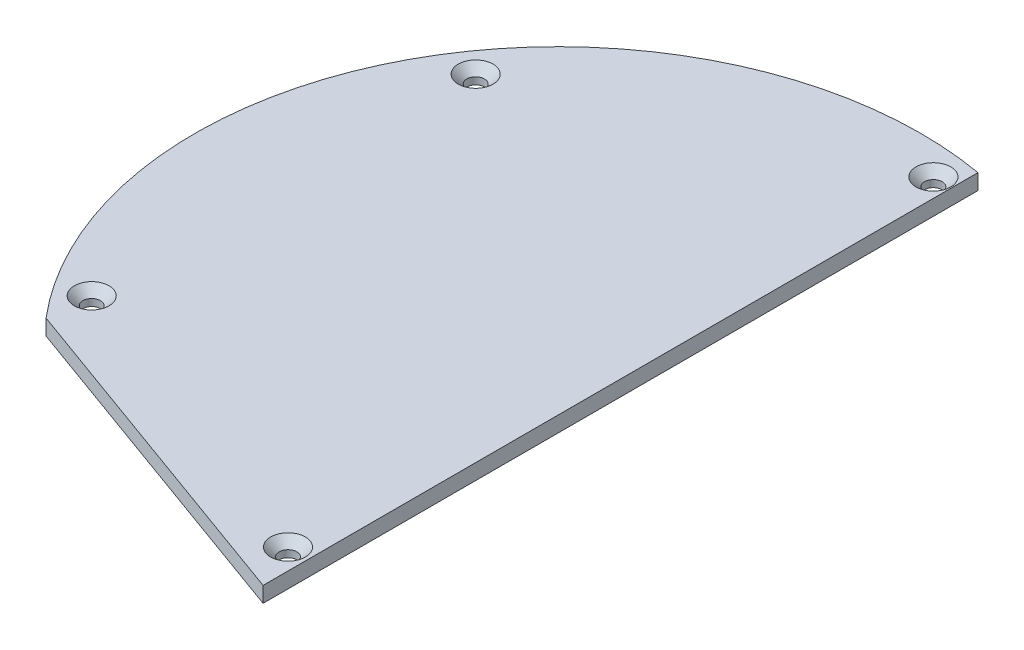
SolidWorks part; units mm, degrees
ref_plane "Front Plane" through (0, 0, 0) normal (0, 0, 1) x (1, 0, 0)
ref_plane "Top Plane" through (0, 0, 0) normal (0, 1, 0) x (1, 0, 0)
ref_plane "Right Plane" through (0, 0, 0) normal (1, 0, 0) x (0, 0, -1)
sketch "Sketch1" plane through (0, 0, 0) normal (0, 1, 0) x (1, 0, 0)
  line L0 (12, 68.9638) -> (12, -68.8024)
  line L1 (12.3, 68.9109) -> (12.3, -68.9109) construction
  line L2 (12, -68.8024) -> (-53.5286, -45.1076)
  line L3 (0, 0) -> (0, 50000) construction
  line L4 (12, -68.8024) -> (12.3, -68.9109) construction
  line L5 (-52.8353, 36.9957) -> (-57.3406, 40.1504) construction
  line L6 (-52.8353, -36.9957) -> (-57.3406, -40.1504) construction
  line L7 (8.4189, 63.9482) -> (9.1368, 69.4011) construction
  arc A0 (12, 68.9638) -> (-53.5286, -45.1076) centre (0, 0) ccw
  arc A1 (12, -68.9638) -> (12, 68.9638) centre (0, 0) ccw construction
  circle A2 centre (8, -60) radius 1.65 construction
  circle A3 centre (-52.8353, -36.9957) radius 1.65 construction
  circle A4 centre (-52.8353, 36.9957) radius 1.65 construction
  circle A5 centre (8.4189, 63.9482) radius 1.65 construction
  point P23 (-52.8353, -36.9957)
  point P24 (8, -60)
  point P25 (8.4189, 63.9482)
  point P26 (-52.8353, 36.9957)
  dimension "D1" = 140
  dimension "D5" = 3.3
  dimension "D2" = 12
  dimension "D3" = 12.3
  dimension "D4" = 70
  dimension "D6" = 8
  dimension "D7" = 60
  dimension "D8" = 5.5
  dimension "D9" = 5.5
  dimension "D10" = 5.5
  dimension "D11" = 7.5
  dimension "D12" = 55
  dimension "D13" = 55
extrude "Boss-Extrude1" add sketch "Sketch1" along normal blind 3
sketch "Sketch2" plane through (0, 3, 0) normal (0, 1, 0) x (1, 0, 0)
  line L0 (12, 68.9638) -> (12, -68.8024)
  line L1 (12.3, 68.9109) -> (12.3, -68.9109) construction
  line L2 (12, -68.8024) -> (-53.5286, -45.1076)
  line L3 (0, 0) -> (0, 50000) construction
  line L4 (12, -68.8024) -> (12.3, -68.9109) construction
  line L5 (-52.8353, 36.9957) -> (-57.3406, 40.1504) construction
  line L6 (-52.8353, -36.9957) -> (-57.3406, -40.1504) construction
  line L7 (8.4189, 63.9482) -> (9.1368, 69.4011) construction
  arc A0 (12, 68.9638) -> (-53.5286, -45.1076) centre (0, 0) ccw
  arc A1 (12, -68.9638) -> (12, 68.9638) centre (0, 0) ccw construction
  circle A2 centre (8, -60) radius 1.65 construction
  circle A3 centre (-52.8353, -36.9957) radius 1.65 construction
  circle A4 centre (-52.8353, 36.9957) radius 1.65 construction
  circle A5 centre (8.4189, 63.9482) radius 1.65 construction
  point P23 (-52.8353, -36.9957)
  point P24 (8, -60)
  point P25 (8.4189, 63.9482)
  point P26 (-52.8353, 36.9957)
  dimension "D1" = 140
  dimension "D5" = 3.3
  dimension "D2" = 12
  dimension "D3" = 12.3
  dimension "D4" = 70
  dimension "D6" = 8
  dimension "D7" = 60
  dimension "D8" = 5.5
  dimension "D9" = 5.5
  dimension "D10" = 5.5
  dimension "D11" = 7.5
  dimension "D12" = 55
  dimension "D13" = 55
hole_wizard "CSK for M3 Flat Head Machine Screw1" positions "Sketch2" profile "Sketch4" countersink size "M3" standard "ANSI Metric" end condition through all
sketch "Sketch4" plane through (-52.8353, 3, -36.9957) normal (1, 0, 0) x (0, 0, 1)
  line L0 (0, 0) -> (0, 3)
  line L1 (0, 3) -> (1.7, 3)
  line L2 (1.7, 3) -> (1.7, 1.65)
  line L3 (1.7, 1.65) -> (3.35, 0)
  line L5 (3.35, 0) -> (0, 0)
  line L6 (-1.7, 1.65) -> (-3.35, 0) construction
  line L11 (0, -6.35) -> (0, 107.95) construction
  dimension "Thru Hole Dia." = 3.4
  dimension "Thru Hole Depth" = 3
  dimension "Near C'Sink Dia." = 6.7
  dimension "Near C'Sink Angle" = 90
